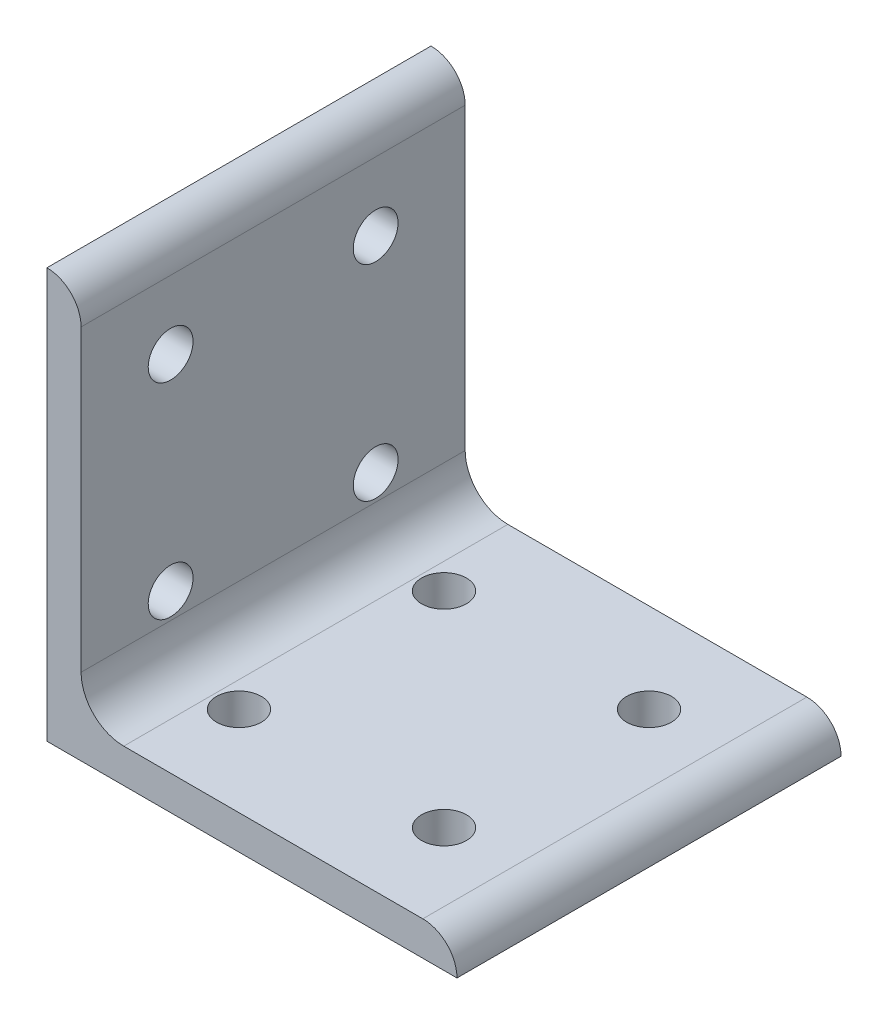
SolidWorks part; units mm, degrees
material "6105-T5 Aluminum"
ref_plane "Front Plane" through (0, 0, 0) normal (0, 0, 1) x (1, 0, 0)
ref_plane "Top Plane" through (0, 0, 0) normal (0, 1, 0) x (1, 0, 0)
ref_plane "Right Plane" through (0, 0, 0) normal (1, 0, 0) x (0, 0, -1)
sketch "Sketch2" plane through (0, 0, 0) normal (0, 0, 1) x (1, 0, 0)
  line L0 (0, 0) -> (0, 76.2)
  line L1 (76.2, 6.35) -> (76.2, 0)
  line L2 (6.35, 76.2) -> (6.35, 14.2748)
  line L3 (14.2748, 6.35) -> (76.2, 6.35)
  line L4 (0, 76.2) -> (6.35, 76.2)
  line L5 (76.2, 0) -> (0, 0)
  arc A2 (6.35, 14.2748) -> (14.2748, 6.35) centre (14.2748, 14.2748) ccw
  dimension "D3" = 76.2
  dimension "D4" = 7.9248
  dimension "D1" = 6.35
  dimension "D2" = 6.35
  dimension "D5" = 76.2
extrude "Boss-Extrude1" add sketch "Sketch2" along normal mid plane 71.374
fillet "Fillet1" radius 6.35
sketch "Sketch3" plane through (0, 0, 0) normal (-1, 0, 0) x (0, 0, 1)
  line L1 (-19.05, 57.15) -> (-19.05, 19.05) construction
  line L2 (0, 64.1778) -> (0, 46.5501) construction
  circle A0 centre (-19.05, 57.15) radius 4.1656
  circle A1 centre (-19.05, 19.05) radius 4.1656
  circle A2 centre (19.05, 19.05) radius 4.1656
  circle A3 centre (19.05, 57.15) radius 4.1656
  dimension "D1" = 8.3312
  dimension "D4" = 38.1
  dimension "D2" = 19.05
  dimension "D3" = 57.15
extrude "Cut-Extrude1" cut sketch "Sketch3" against normal through all
sketch "Sketch4" plane through (0, 0, 0) normal (0, -1, 0) x (1, 0, 0)
  line L0 (19.05, 19.05) -> (57.15, 19.05) construction
  line L2 (64.9613, 0) -> (34.7851, 0) construction
  circle A0 centre (57.15, 19.05) radius 4.1656
  circle A1 centre (19.05, -19.05) radius 4.1656
  circle A2 centre (57.15, -19.05) radius 4.1656
  circle A3 centre (19.05, 19.05) radius 4.1656
  dimension "D1" = 8.3312
  dimension "D2" = 19.05
  dimension "D3" = 38.1
  dimension "D4" = 19.05
extrude "Cut-Extrude2" cut sketch "Sketch4" against normal up to next
